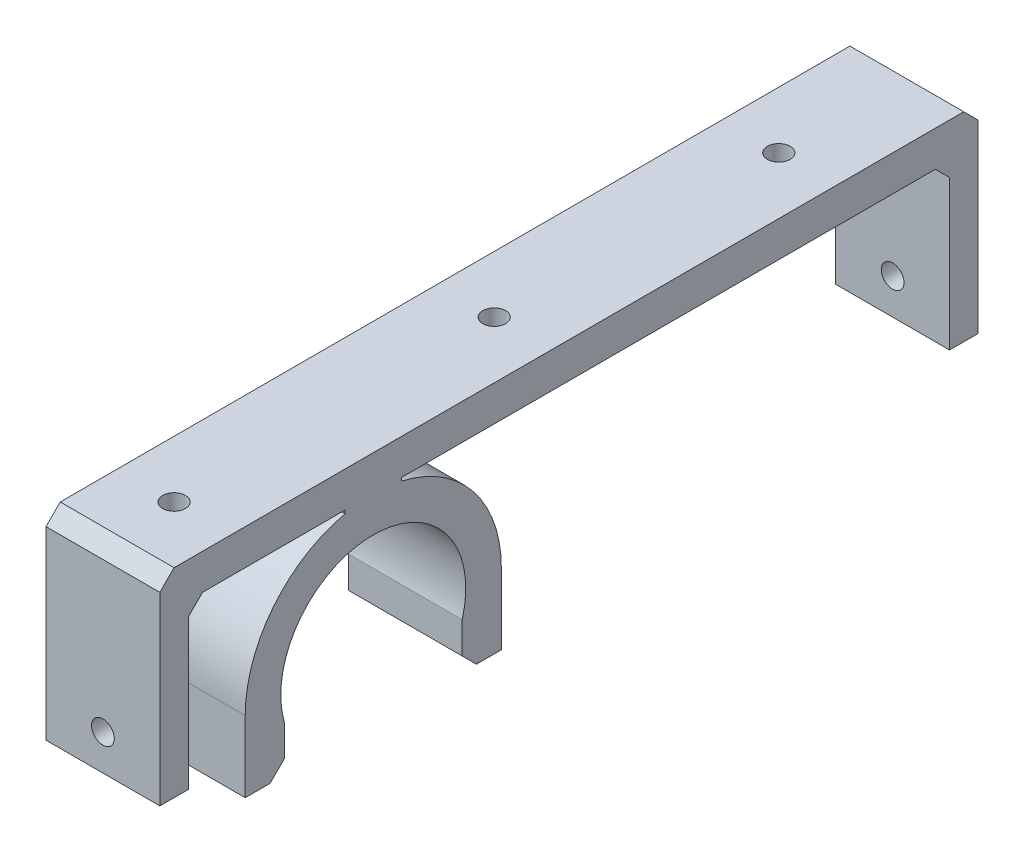
SolidWorks part; units mm, degrees
ref_plane "前视基准面" through (0, 0, 0) normal (0, 0, 1) x (1, 0, 0)
ref_plane "上视基准面" through (0, 0, 0) normal (0, 1, 0) x (1, 0, 0)
ref_plane "右视基准面" through (0, 0, 0) normal (1, 0, 0) x (0, 0, -1)
sketch "Sketch1" plane through (0, 0, 0) normal (1, 0, 0) x (0, 0, -1)
  line L0 (-12.5, -3.5707) -> (-12.5, -10)
  line L1 (-18, 0) -> (-18, -10)
  line L2 (-18, -10) -> (-12.5, -10)
  line L3 (12.5, -3.5707) -> (12.5, -10)
  line L4 (-4, 18) -> (-26, 18)
  line L5 (18, -10) -> (18, 0)
  line L6 (12.5, -10) -> (18, -10)
  line L7 (-30, 18) -> (-30, 23)
  line L8 (-30, 23) -> (85, 23)
  line L9 (85, 23) -> (85, 18)
  line L10 (81, 18) -> (4, 18)
  line L11 (0, 0) -> (0, 36.0866) construction
  line L12 (85, 18) -> (85, -5)
  line L13 (85, -5) -> (81, -5)
  line L14 (81, -5) -> (81, 18)
  line L15 (-30, 18) -> (-30, -5)
  line L16 (-30, -5) -> (-26, -5)
  line L17 (-26, -5) -> (-26, 18)
  arc A0 (12.5, -3.5707) -> (-12.5, -3.5707) centre (0, 0) ccw
  arc A1 (18, 0) -> (3.9752, 17.5556) centre (0, 0) ccw
  arc A2 (3.9752, 17.5556) -> (4, 18) centre (0, 18) ccw
  arc A3 (-4, 18) -> (-3.9752, 17.5556) centre (0, 18) ccw
  arc A4 (-3.9752, 17.5556) -> (-18, 0) centre (0, 0) ccw
  dimension "D1" = 13
  dimension "D2" = 18
  dimension "D3" = 10
  dimension "D4" = 8
  dimension "D5" = 30
  dimension "D6" = 85
  dimension "D7" = 5
  dimension "D8" = 4
  dimension "D9" = 4
  dimension "D10" = 5
  dimension "D11" = 28
extrude "Boss-Extrude1" add sketch "Sketch1" along normal mid plane 16
chamfer "Chamfer1" distance 2 angle 45 2 edges at (0, 18, -81) (0, 18, 26)
chamfer "Chamfer2" distance 2 angle 45 4 edges at (0, -10, -12.5) (0, -10, 12.5) (0, 23, -85) (0, 23, 30)
sketch "Sketch2" plane through (0, 0, 30) normal (0, 0, 1) x (1, 0, 0)
  circle A0 centre (0, 0) radius 1.6
  dimension "D1" = 3.2
extrude "Cut-Extrude1" cut sketch "Sketch2" against normal up to next
sketch "Sketch3" plane through (0, 0, -85) normal (0, 0, -1) x (-1, 0, 0)
  circle A0 centre (0, 0) radius 1.6
  dimension "D1" = 3.2
extrude "Cut-Extrude2" cut sketch "Sketch3" against normal up to next
sketch "Sketch4" plane through (0, 23, 0) normal (0, 1, 0) x (1, 0, 0)
  circle A0 centre (0, 65) radius 1.6
  circle A1 centre (0, 25) radius 1.6
  circle A2 centre (0, -20) radius 1.6
  point P6 (0, 0)
  point P7 (0, 0)
  point P9 (0, -13.7632)
  dimension "D3" = 3.2
  dimension "D1" = 40
  dimension "D2" = 85
  dimension "D4" = 20
extrude "Cut-Extrude3" cut sketch "Sketch4" against normal up to next
